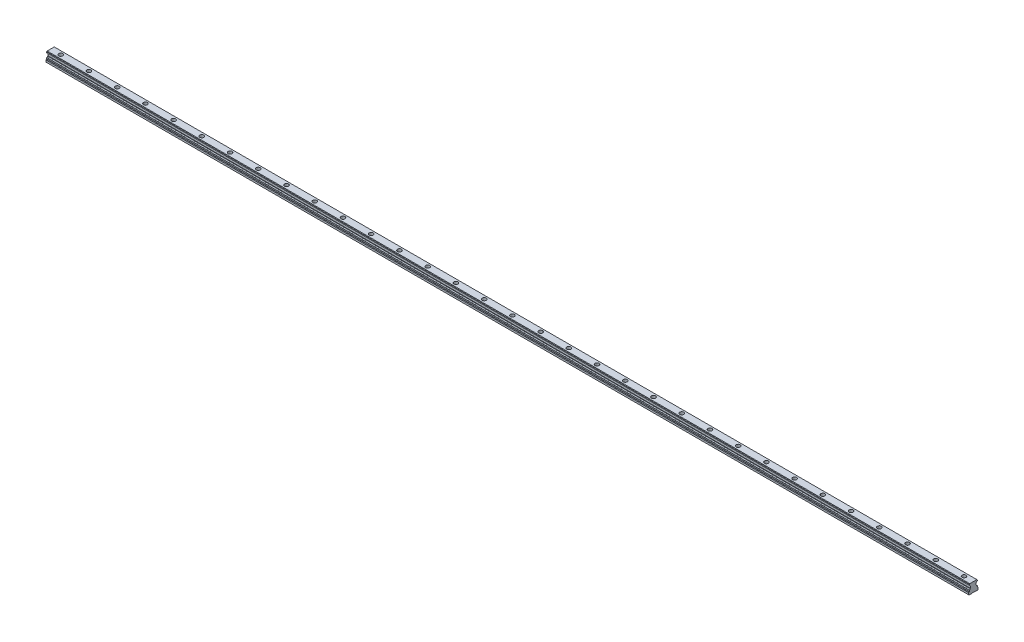
SolidWorks part; units mm, degrees
ref_plane "Front Plane" through (0, 0, 0) normal (0, 0, 1) x (1, 0, 0)
ref_plane "Top Plane" through (0, 0, 0) normal (0, 1, 0) x (1, 0, 0)
ref_plane "Right Plane" through (0, 0, 0) normal (1, 0, 0) x (0, 0, -1)
ref_plane "Plane1" through (58.5, 0, 0) normal (1, 0, 0) x (0, 0, -1)
sketch "Sketch7" plane through (58.5, 0, 0) normal (1, 0, 0) x (0, 0, -1)
  line L30 (-7.709, 8.8831) -> (-8.5, 8.6011)
  line L32 (-8.75, 5.6717) -> (-10, 4.95)
  line L35 (-10, 4.95) -> (-10, 1)
  line L37 (-10, 1) -> (-9, 0)
  line L39 (-4, 0) -> (-3.5, 0.5)
  line L42 (-3.5, 0.5) -> (3.5, 0.5)
  line L48 (3.5, 0.5) -> (4, 0)
  line L52 (4, 0) -> (9, 0)
  line L57 (-8.5, 8.6011) -> (-8.5, 6.1047)
  line L61 (-9, 0) -> (-4, 0)
  line L69 (8.5, 6.1047) -> (8.5, 8.4669)
  line L71 (6.5033, 10.3667) -> (6, 10.87)
  line L72 (6, 10.87) -> (6, 14.93)
  line L73 (6, 14.93) -> (6.5033, 15.4333)
  line L75 (8.5, 17.1989) -> (8.5, 19.3)
  line L77 (7.5, 20.3) -> (-7.5, 20.3)
  line L79 (-8.5, 19.3) -> (-8.5, 17.3331)
  line L81 (-6.5033, 15.4333) -> (-6, 14.93)
  line L82 (-6, 14.93) -> (-6, 10.87)
  line L83 (-6, 10.87) -> (-6.5033, 10.3667)
  line L85 (9, 0) -> (10, 1)
  line L87 (10, 1) -> (10, 4.95)
  line L89 (10, 4.95) -> (8.75, 5.6717)
  line L91 (8.5, 8.4669) -> (8.0847, 8.8822)
  line L93 (7.709, 16.9169) -> (8.5, 17.1989)
  line L95 (8.5, 19.3) -> (7.5, 20.3)
  line L97 (-7.5, 20.3) -> (-8.5, 19.3)
  line L99 (-8.5, 17.3331) -> (-8.0847, 16.9178)
  arc A8 (-8.75, 5.6717) -> (-8.5, 6.1047) centre (-9, 6.1047) ccw
  arc A12 (-7.709, 8.8831) -> (-6.5033, 10.3667) centre (-7.9, 10.27) ccw
  arc A15 (6.5033, 10.3667) -> (8.0847, 8.8822) centre (7.9, 10.27) ccw
  arc A16 (7.709, 16.9169) -> (6.5033, 15.4333) centre (7.9, 15.53) ccw
  arc A17 (-6.5033, 15.4333) -> (-8.0847, 16.9178) centre (-7.9, 15.53) ccw
  arc A19 (8.5, 6.1047) -> (8.75, 5.6717) centre (9, 6.1047) ccw
sketch "Sketch1" [suppressed] plane through (58.5, 0, 0) normal (1, 0, 0) x (0, 0, -1)
  line L0 (-8.5, 0) -> (8.5, 0)
  line L1 (8.5, 0) -> (8.5, 9.0051)
  line L2 (6.5033, 10.3667) -> (6, 10.87)
  line L3 (6, 10.87) -> (6, 14.93)
  line L4 (6, 14.93) -> (6.5033, 15.4333)
  line L5 (8.5, 16.7949) -> (8.5, 20.3)
  line L6 (8.5, 20.3) -> (-8.5, 20.3)
  line L7 (-8.5, 20.3) -> (-8.5, 16.7949)
  line L8 (-6.5033, 15.4333) -> (-6, 14.93)
  line L9 (-6, 14.93) -> (-6, 10.87)
  line L10 (-6, 10.87) -> (-6.5033, 10.3667)
  line L11 (-8.5, 9.0051) -> (-8.5, 0)
  arc A0 (8.5, 9.0051) -> (6.5033, 10.3667) centre (7.9, 10.27) cw
  arc A1 (6.5033, 15.4333) -> (8.5, 16.7949) centre (7.9, 15.53) cw
  arc A2 (-8.5, 16.7949) -> (-6.5033, 15.4333) centre (-7.9, 15.53) cw
  arc A3 (-6.5033, 10.3667) -> (-8.5, 9.0051) centre (-7.9, 10.27) cw
extrude "Boss-Extrude5" add sketch "Sketch7" along normal blind 1961
sketch "Sketch8" plane through (0, 20.3, 0) normal (0, 1, 0) x (1, 0, 0)
  circle A0 centre (1999.7779, 0) radius 4.25
  dimension "D1" = 8.5
extrude "Cut-Extrude1" cut sketch "Sketch8" against normal blind 9
sketch "Sketch9" plane through (0, 11.3, 0) normal (0, 1, 0) x (1, 0, 0)
  circle A0 centre (1999.7779, 0) radius 3
  dimension "D1" = 6
extrude "Cut-Extrude2" cut sketch "Sketch9" against normal through all
pattern_linear "LPattern1" count 35 spacing 60 along (-1, 0, 0) of "Cut-Extrude1", "Cut-Extrude2"
